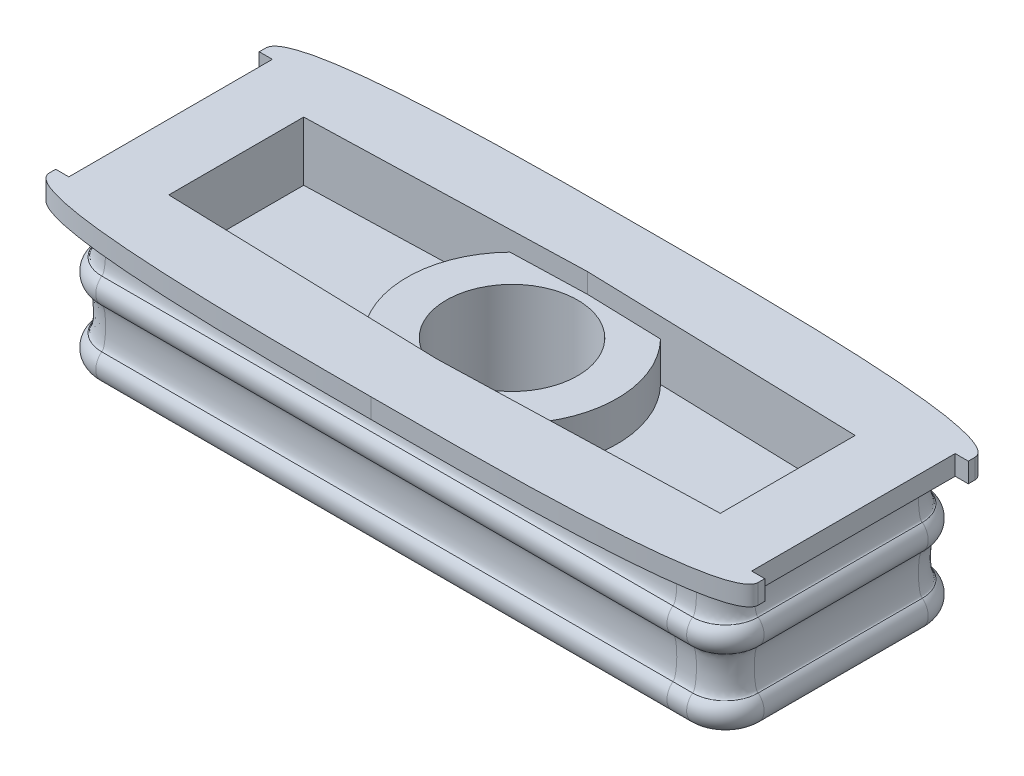
SolidWorks part; units mm, degrees
material "Silicon Rubber"
ref_plane "Front Plane" through (0, 0, 0) normal (0, 0, 1) x (1, 0, 0)
ref_plane "Top Plane" through (0, 0, 0) normal (0, 1, 0) x (1, 0, 0)
ref_plane "Right Plane" through (0, 0, 0) normal (1, 0, 0) x (0, 0, -1)
sketch "Sketch1" plane through (0, 0, 0) normal (0, 1, 0) x (1, 0, 0)
  line L1 (0, 0) -> (12.7, 0)
  line L2 (0, 0) -> (0, 4.445)
  line L3 (0, 4.445) -> (12.7, 4.445)
  line L4 (12.7, 0) -> (12.7, 4.445)
  dimension "D1" = 4.445
  dimension "D2" = 12.7
extrude "Boss-Extrude1" add sketch "Sketch1" along normal blind 2.54
sketch "Sketch2" plane through (0, 2.54, 0) normal (0, 1, 0) x (1, 0, 0)
  line L0 (-0.254, 4.191) -> (-0.254, 0.254)
  line L1 (-0.254, 0.254) -> (-0.508, 0.254)
  line L2 (-0.508, 0.254) -> (-0.508, 0.127)
  line L3 (-0.508, 4.953) -> (13.208, 4.953) construction
  line L4 (-0.508, 4.953) -> (-0.508, -0.508) construction
  line L5 (-0.508, -0.508) -> (13.208, -0.508) construction
  line L6 (13.208, 4.953) -> (13.208, -0.508) construction
  line L7 (-0.508, 4.953) -> (13.208, -0.508) construction
  line L8 (-0.508, -0.508) -> (13.208, 4.953) construction
  line L9 (-0.254, 4.191) -> (-0.508, 4.191)
  line L10 (12.7, 4.445) -> (0, 4.445) construction
  line L11 (-0.508, 4.191) -> (-0.508, 4.318)
  line L12 (6.35, 4.445) -> (6.35, 0) construction
  line L13 (0, 0) -> (12.7, 0) construction
  line L14 (13.208, 4.953) -> (13.208, -0.508) construction
  line L15 (13.208, 4.191) -> (13.208, 4.318)
  line L16 (-0.508, 2.2225) -> (13.208, 2.2225) construction
  line L17 (0, 4.445) -> (0, 0) construction
  line L18 (12.954, 4.191) -> (13.208, 4.191)
  line L19 (13.208, 0.254) -> (13.208, 0.127)
  line L20 (12.954, 0.254) -> (13.208, 0.254)
  line L21 (12.954, 4.191) -> (12.954, 0.254)
  spline S0 degree 3 poles (-0.508, 0.127) (-0.508, -0.5285) (4.2726, -0.508) (6.35, -0.508) knots 0 0 0 0 1 1 1 1
  spline S1 degree 3 poles (-0.508, 4.318) (-0.508, 4.9735) (4.2726, 4.953) (6.35, 4.953) knots 0 0 0 0 1 1 1 1
  spline S2 degree 3 poles (13.208, 4.318) (13.208, 4.9735) (8.4274, 4.953) (6.35, 4.953) knots 0 0 0 0 1 1 1 1
  spline S3 degree 3 poles (13.208, 0.127) (13.208, -0.5285) (8.4274, -0.508) (6.35, -0.508) knots 0 0 0 0 1 1 1 1
  point P2 (6.35, 2.2225)
  point P22 (-0.254, 2.2225)
  point P34 (12.954, 2.2225)
  dimension "D1" = 13.716
  dimension "D2" = 5.461
  dimension "D3" = 0.254
  dimension "D4" = 0.254
  dimension "D5" = 0.127
extrude "Boss-Extrude2" add sketch "Sketch2" along normal blind 0.381
sketch "Sketch3" plane through (0, 2.921, 0) normal (0, 1, 0) x (1, 0, 0)
  line L0 (12.954, 2.2225) -> (-0.254, 2.2225) construction
  line L3 (12.954, 0.254) -> (12.954, 4.191) construction
  line L4 (-0.254, 4.191) -> (-0.254, 0.254) construction
  circle A0 centre (6.35, 2.2225) radius 1.27
  dimension "D1" = 2.54
extrude "Cut-Extrude1" cut sketch "Sketch3" against normal through all
sketch "Sketch4" plane through (0, 2.921, 0) normal (0, 1, 0) x (1, 0, 0)
  line L0 (11.684, 3.5271) -> (11.684, 0.9179)
  line L1 (12.954, 0.254) -> (12.954, 4.191) construction
  line L2 (6.35, 4.953) -> (6.35, -0.508) construction
  line L3 (6.35, 3.683) -> (11.684, 3.5271)
  line L4 (11.684, 4.7971) -> (11.684, 3.5271) construction
  line L5 (11.684, 0.9179) -> (6.35, 0.762)
  line L6 (11.684, 0.9179) -> (11.684, -0.3521) construction
  line L7 (1.016, 0.9179) -> (1.016, -0.3521) construction
  line L8 (1.016, 4.7971) -> (1.016, 3.5271) construction
  line L9 (1.016, 0.9179) -> (6.35, 0.762)
  line L10 (6.35, 3.683) -> (1.016, 3.5271)
  line L11 (1.016, 3.5271) -> (1.016, 0.9179)
  spline S0 degree 3 poles (6.35, -0.508) (8.4274, -0.508) (13.208, -0.5285) (13.208, 0.127) knots 0 0 0 0 1 1 1 1 construction
  spline S52 degree 3 poles (13.208, 4.318) (13.208, 4.9735) (8.4274, 4.953) (6.35, 4.953) knots 0 0 0 0 1 1 1 1 construction
  dimension "D2" = 1.27
  dimension "D1" = 1.27
  dimension "D3" = 1.27
  dimension "D4" = 1.27
extrude "Cut-Extrude2" cut sketch "Sketch4" against normal blind 1.143
sketch "Sketch5" plane through (0, 1.778, 0) normal (0, 1, 0) x (1, 0, 0)
  circle A0 centre (6.35, 2.2225) radius 1.27 construction
  circle A1 centre (6.35, 2.2225) radius 1.27
  circle A2 centre (6.35, 2.2225) radius 2.032
  dimension "D1" = 0.762
extrude "Boss-Extrude3" add sketch "Sketch5" along normal blind 0.762
fillet "Fillet1" radius 0.635 4 edges at (12.7, 1.27, -4.445) (12.7, 1.27, 0) (0, 1.27, 0) (0, 1.27, -4.445)
sketch "Sketch8" plane through (0, 0, 0) normal (0, -1, 0) x (-1, 0, 0)
  line L4 (-0.635, 4.445) -> (-12.065, 4.445)
  line L5 (-12.7, 3.81) -> (-12.7, 0.635)
  line L6 (-12.065, 0) -> (-0.635, 0)
  line L7 (0, 0.635) -> (0, 3.81)
  line L8 (-0.635, 4.445) -> (-12.065, 4.445)
  line L9 (-12.7, 3.81) -> (-12.7, 0.635)
  line L10 (-12.065, 0) -> (-0.635, 0)
  line L11 (0, 0.635) -> (0, 3.81)
  arc A4 (-12.065, 4.445) -> (-12.7, 3.81) centre (-12.065, 3.81) ccw
  arc A5 (-12.7, 0.635) -> (-12.065, 0) centre (-12.065, 0.635) ccw
  arc A6 (-0.635, 0) -> (0, 0.635) centre (-0.635, 0.635) ccw
  arc A7 (0, 3.81) -> (-0.635, 4.445) centre (-0.635, 3.81) ccw
  arc A8 (-12.065, 4.445) -> (-12.7, 3.81) centre (-12.065, 3.81) ccw
  arc A9 (-12.7, 0.635) -> (-12.065, 0) centre (-12.065, 0.635) ccw
  arc A10 (-0.635, 0) -> (0, 0.635) centre (-0.635, 0.635) ccw
  arc A11 (0, 3.81) -> (-0.635, 4.445) centre (-0.635, 3.81) ccw
  dimension "D1" = 0
sketch "Sketch9" plane through (11.684, 0, 0) normal (-1, 0, 0) x (0, 0, 1)
  line L1 (-0.2032, 0) -> (-0.2032, 2.5469) construction
  line L2 (0, 0) -> (0, 2.54) construction
  line L3 (-0.635, 2.54) -> (-3.81, 2.54) construction
  line L4 (-3.81, 0) -> (-0.635, 0) construction
  circle A0 centre (-0.2032, 0.3175) radius 0.3175
  circle A1 centre (-0.2032, 0.9525) radius 0.3175 construction
  circle A2 centre (-0.2032, 1.5875) radius 0.3175
  circle A3 centre (-0.2032, 2.2225) radius 0.3175 construction
  dimension "D1" = 0.2032
sweep "Sweep13" add profiles "Sketch9" path "Sketch8"
sketch "Sketch10" plane through (11.684, 0, 0) normal (-1, 0, 0) x (0, 0, 1)
  line L1 (0, 1.8315) -> (0, 2.54)
  line L2 (0, 0.5615) -> (0, 1.3435)
  ellipse E0 centre (0, 2.1857) end of major axis (0, 2.54) minor radius 0.0762 (0, 1.8315) -> (0, 2.54) cw
  ellipse E1 centre (0, 0.9525) end of major axis (0, 1.3435) minor radius 0.0762 (0, 0.5615) -> (0, 1.3435) cw
  dimension "D1" = 0.0762
sketch "Sketch11" plane through (0, 0, 0) normal (0, -1, 0) x (1, 0, 0)
  line L0 (0, -3.81) -> (0, -0.635) construction
  line L1 (12.7, -0.635) -> (12.7, -3.81) construction
  line L2 (0.635, 0) -> (12.065, 0) construction
  line L3 (12.065, -4.445) -> (0.635, -4.445) construction
  line L4 (0, -3.81) -> (0, -0.635)
  line L5 (12.7, -0.635) -> (12.7, -3.81)
  line L6 (0.635, 0) -> (12.065, 0)
  line L7 (12.065, -4.445) -> (0.635, -4.445)
  arc A0 (0.635, 0) -> (0, -0.635) centre (0.635, -0.635) ccw construction
  arc A1 (0, -3.81) -> (0.635, -4.445) centre (0.635, -3.81) ccw construction
  arc A2 (12.065, -4.445) -> (12.7, -3.81) centre (12.065, -3.81) ccw construction
  arc A3 (12.7, -0.635) -> (12.065, 0) centre (12.065, -0.635) ccw construction
  arc A4 (0.635, 0) -> (0, -0.635) centre (0.635, -0.635) ccw
  arc A5 (0, -3.81) -> (0.635, -4.445) centre (0.635, -3.81) ccw
  arc A6 (12.065, -4.445) -> (12.7, -3.81) centre (12.065, -3.81) ccw
  arc A7 (12.7, -0.635) -> (12.065, 0) centre (12.065, -0.635) ccw
sweep "Cut-Sweep9" cut profiles "Sketch10" path "Sketch11"
fillet "Fillet2" radius 0.635 8 edges at (12.514, 0, -0.186) (6.35, 0, 0) (0.186, 0, -0.186) (0, 0, -2.2225) (0.186, 0, -4.259) (6.35, 0, -4.445) (12.514, 0, -4.259) (12.7, 0, -2.2225)
